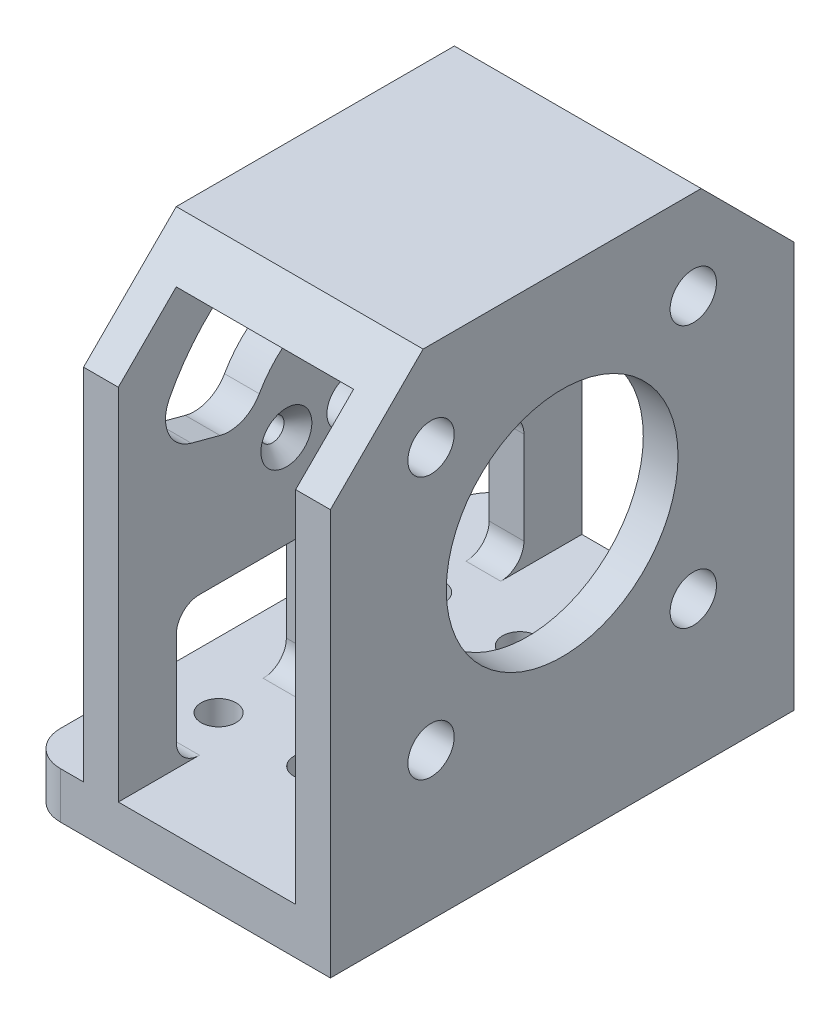
SolidWorks part; units mm, degrees
material "6061 合金"
ref_plane "前视基准面" through (0, 0, 0) normal (0, 0, 1) x (1, 0, 0)
ref_plane "上视基准面" through (0, 0, 0) normal (0, 1, 0) x (1, 0, 0)
ref_plane "右视基准面" through (0, 0, 0) normal (1, 0, 0) x (0, 0, -1)
sketch "草图1" plane through (0, 0, 0) normal (0, 1, 0) x (1, 0, 0)
  line L1 (-10.65, -20) -> (10.65, -20)
  line L2 (-10.65, -20) -> (-10.65, 20)
  line L3 (-10.65, 20) -> (10.65, 20)
  line L4 (10.65, -20) -> (10.65, 20)
  line L5 (-10.65, -20) -> (10.65, 20) construction
  line L6 (-10.65, 20) -> (10.65, -20) construction
  point P0 (0, 0)
  dimension "D1" = 21.3
  dimension "D2" = 40
extrude "凸台-拉伸1" add sketch "草图1" along normal blind 4
sketch "草图2" plane through (0, 4, 0) normal (0, 1, 0) x (1, 0, 0)
  line L0 (-10.65, -20) -> (10.65, -20) construction
  line L1 (-10.65, 20) -> (-7.65, 20)
  line L2 (-10.65, 20) -> (-10.65, -20)
  line L3 (-10.65, -20) -> (-7.65, -20)
  line L4 (-7.65, 20) -> (-7.65, -20)
  line L6 (10.65, 20) -> (7.65, 20)
  line L7 (10.65, 20) -> (10.65, -20)
  line L8 (10.65, -20) -> (7.65, -20)
  line L9 (7.65, 20) -> (7.65, -20)
  dimension "D1" = 3
  dimension "D2" = 3
extrude "凸台-拉伸2" add sketch "草图2" along normal blind 36
sketch "草图3" plane through (0, 40, 0) normal (0, 1, 0) x (1, 0, 0)
  line L1 (-10.65, 20) -> (10.65, 20)
  line L2 (-10.65, 20) -> (-10.65, -20)
  line L3 (-10.65, -20) -> (10.65, -20)
  line L4 (10.65, 20) -> (10.65, -20)
extrude "凸台-拉伸3" add sketch "草图3" along normal blind 3
sketch "草图4" plane through (10.65, 0, 0) normal (1, 0, 0) x (0, 0, -1)
  line L0 (0, 0) -> (0, 43) construction
  line L1 (-20, 43) -> (20, 43) construction
  line L2 (-20, 0) -> (20, 0) construction
  circle A0 centre (0, 24) radius 10
  dimension "D1" = 24
  dimension "D2" = 20
extrude "切除-拉伸1" cut sketch "草图4" against normal up to next
sketch "草图5" plane through (10.65, 0, 0) normal (1, 0, 0) x (0, 0, -1)
  line L0 (-20, 35) -> (-12, 43)
  line L1 (-20, 43) -> (-20, 0) construction
  line L2 (-20, 43) -> (20, 43) construction
  line L3 (-20, 35) -> (-20, 43)
  line L4 (-20, 43) -> (-12, 43)
  line L5 (0, 43) -> (0, 0) construction
  line L6 (20, 35) -> (20, 43)
  line L7 (20, 35) -> (12, 43)
  line L8 (20, 43) -> (12, 43)
  dimension "D1" = 8
  dimension "D2" = 8
extrude "切除-拉伸2" cut sketch "草图5" against normal through all
sketch "草图13" plane through (-10.65, 0, 0) normal (-1, 0, 0) x (0, 0, 1)
  line L1 (-20, 0) -> (20, 0)
  line L2 (-20, 0) -> (-20, 4)
  line L3 (-20, 4) -> (20, 4)
  line L4 (20, 0) -> (20, 4)
extrude "凸台-拉伸4" add sketch "草图13" along normal blind 5
sketch "草图6" plane through (0, 4, 0) normal (0, 1, 0) x (1, 0, 0)
  line L0 (-6, -20) -> (-6, 20) construction
  line L3 (-10.65, 0) -> (10.65, 0) construction
  line L8 (-10.65, 20) -> (-10.65, -20) construction
  line L9 (-10, -9) -> (-2, -9) construction
  line L10 (-10.65, 12) -> (-10.65, -12) construction
  line L11 (10.65, -12) -> (10.65, 12) construction
  line L12 (-7.65, -20) -> (7.65, -20) construction
  line L13 (7.65, 20) -> (-7.65, 20) construction
  line L16 (-10, -9) -> (-10, 9) construction
  line L17 (-10, 9) -> (-2, 9) construction
  line L18 (-2, -9) -> (-2, 9) construction
  line L19 (-10, -9) -> (-2, 9) construction
  line L20 (-10, 9) -> (-2, -9) construction
  circle A4 centre (-10, 9) radius 1.5
  circle A5 centre (-2, 9) radius 1.5
  circle A6 centre (-2, -9) radius 1.5
  circle A7 centre (-10, -9) radius 1.5
  point P6 (0, 0)
  point P7 (-6, 0)
  dimension "D3" = 3
  dimension "D1" = 8
  dimension "D2" = 18
  dimension "D4" = 4.65
extrude "切除-拉伸3" cut sketch "草图6" against normal through all
sketch "草图7" plane through (10.65, 0, 0) normal (1, 0, 0) x (0, 0, -1)
  line L0 (0, 24) -> (0, 40) construction
  line L1 (0, 24) -> (-11.3137, 35.3137) construction
  circle A0 centre (0, 24) radius 16 construction
  circle A1 centre (-11.3137, 35.3137) radius 2
  circle A2 centre (11.3137, 35.3137) radius 2
  circle A3 centre (11.3137, 12.6863) radius 2
  circle A4 centre (-11.3137, 12.6863) radius 2
  point P15 (0, 24)
  dimension "D1" = 32
  dimension "D3" = 4
  dimension "D2" = 45
  dimension "D4" = 4
extrude "切除-拉伸4" cut sketch "草图7" against normal blind 4
sketch "草图9" plane through (-10.65, 0, 0) normal (-1, 0, 0) x (0, 0, 1)
  circle A0 centre (0, 24) radius 2
  circle A1 centre (0, 24) radius 5.5 construction
  circle A2 centre (-5.5, 24) radius 1
  circle A4 centre (5.5, 24) radius 1
  circle A6 centre (0, 29.5) radius 1 [skipped]
  circle A7 centre (0, 18.5) radius 1 [skipped]
  point P15 (0, 24)
  dimension "D1" = 4
  dimension "D2" = 11
  dimension "D3" = 2
  dimension "D4" = 4
extrude "切除-拉伸6" cut sketch "草图9" against normal blind 4
sketch "草图10" plane through (-10.65, 0, 0) normal (-1, 0, 0) x (0, 0, 1)
  line L0 (0, 33) -> (0, 41.5) construction
  line L1 (-2.3294, 32.6933) -> (-4.5293, 40.9037)
  line L2 (2.3294, 32.6933) -> (4.5293, 40.9037)
  line L3 (8.6933, 26.3294) -> (16.9037, 28.5293)
  line L4 (8.6933, 21.6706) -> (16.9037, 19.4707) construction
  line L5 (2.3294, 15.3067) -> (4.5293, 7.0963) construction
  line L6 (-2.3294, 15.3067) -> (-4.5293, 7.0963) construction
  line L7 (-8.6933, 21.6706) -> (-16.9037, 19.4707) construction
  line L8 (-8.6933, 26.3294) -> (-16.9037, 28.5293)
  line L9 (0, 24) -> (-8.6933, 26.3294) construction
  line L10 (-2.3294, 32.6933) -> (0, 24) construction
  line L11 (2.3294, 32.6933) -> (0, 24) construction
  line L12 (8.6933, 26.3294) -> (0, 24) construction
  arc A0 (-8.6933, 21.6706) -> (-2.3294, 15.3067) centre (0, 24) ccw construction
  arc A1 (-16.9037, 19.4707) -> (-4.5293, 7.0963) centre (0, 24) ccw construction
  arc A2 (2.3294, 15.3067) -> (8.6933, 21.6706) centre (0, 24) ccw construction
  arc A3 (4.5293, 7.0963) -> (16.9037, 19.4707) centre (0, 24) ccw construction
  arc A4 (8.6933, 26.3294) -> (2.3294, 32.6933) centre (0, 24) ccw
  arc A5 (16.9037, 28.5293) -> (4.5293, 40.9037) centre (0, 24) ccw
  arc A6 (-2.3294, 32.6933) -> (-8.6933, 26.3294) centre (0, 24) ccw
  arc A7 (-4.5293, 40.9037) -> (-16.9037, 28.5293) centre (0, 24) ccw
  point P16 (0, 24)
  dimension "D1" = 35
  dimension "D2" = 18
  dimension "D3" = 15
  dimension "D4" = 4
extrude "切除-拉伸7" cut sketch "草图10" against normal blind 4
fillet "圆角1" radius 3 8 edges at (-9.15, 26.3294, -8.6933) (-9.15, 32.6933, -2.3294) (-9.15, 28.5293, 16.9037) (-9.15, 26.3294, 8.6933) (-9.15, 32.6933, 2.3294) (-8.65, 40.9037, 4.5293) (-8.65, 40.9037, -4.5293) (-9.15, 28.5293, -16.9037)
sketch "草图11" plane through (-10.65, 0, 0) normal (-1, 0, 0) x (0, 0, 1)
  line L0 (0, 0) -> (0, 43) construction
  line L1 (-20, 0) -> (20, 0) construction
  line L2 (-12, 43) -> (12, 43) construction
  line L12 (20, 4) -> (-20, 4) construction
  line L13 (-15, 4) -> (-2.5, 4)
  line L14 (-15, 4) -> (-15, 16)
  line L15 (-15, 16) -> (-2.5, 16)
  line L16 (-2.5, 4) -> (-2.5, 16)
  line L17 (-20, 35) -> (-20, 4) construction
  line L18 (15, 16) -> (2.5, 16)
  line L19 (2.5, 4) -> (2.5, 16)
  line L20 (15, 4) -> (2.5, 4)
  line L21 (15, 4) -> (15, 16)
  dimension "D1" = 5
  dimension "D2" = 2.5
  dimension "D3" = 12
extrude "切除-拉伸8" cut sketch "草图11" against normal blind 3
fillet "圆角2" radius 2 8 edges at (-9.15, 4, -2.5) (-9.15, 16, -2.5) (-9.15, 16, -15) (-9.15, 4, -15) (-9.15, 16, 2.5) (-9.15, 16, 15) (-9.15, 4, 15) (-9.15, 4, 2.5)
sketch "草图12" plane through (-10.65, 0, 0) normal (-1, 0, 0) x (0, 0, 1)
  circle A0 centre (0, 24) radius 5.75 construction
  circle A1 centre (0, 29.75) radius 1
  circle A2 centre (0, 18.25) radius 1
  dimension "D1" = 11.5
  dimension "D2" = 2
  dimension "D3" = 2
extrude "切除-拉伸9" cut sketch "草图12" against normal blind 3
chamfer "倒角1" distance 1.2 angle 45 4 edges at (-7.65, 24, -4.5) (-7.65, 24, 6.5) (-7.65, 29.75, 1) (-7.65, 18.25, 1)
fillet "圆角3" radius 3 2 edges at (-15.65, 2, 20) (-15.65, 2, -20)
